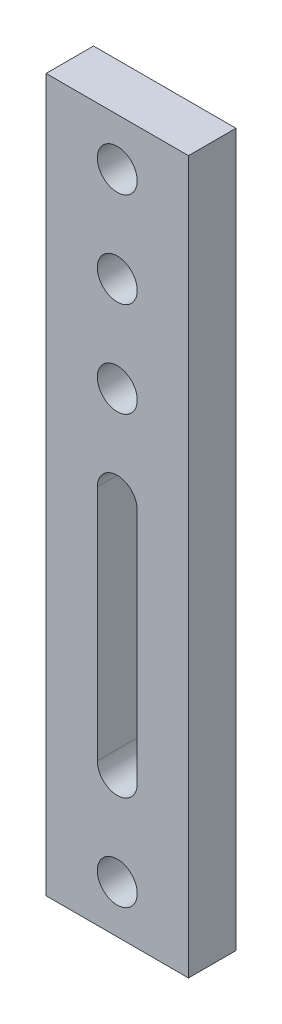
SolidWorks part; units mm, degrees
material "Простая углеродистая сталь"
ref_plane "Спереди" through (0, 0, 0) normal (0, 0, 1) x (1, 0, 0)
ref_plane "Сверху" through (0, 0, 0) normal (0, 1, 0) x (1, 0, 0)
ref_plane "Справа" through (0, 0, 0) normal (1, 0, 0) x (0, 0, -1)
sketch "Эскиз1" plane through (0, 0, 0) normal (0, 0, 1) x (1, 0, 0)
  line L1 (0, 0) -> (75, 0)
  line L2 (0, 0) -> (0, 375)
  line L3 (0, 375) -> (75, 375)
  line L4 (75, 0) -> (75, 375)
  dimension "D1" = 75
  dimension "D2" = 375
extrude "Бобышка-Вытянуть1" add sketch "Эскиз1" along normal blind 25
sketch "Эскиз2" plane through (0, 0, 25) normal (0, 0, 1) x (1, 0, 0)
  line L1 (27, 75) -> (27, 200)
  line L2 (48, 75) -> (48, 200)
  line L3 (0, 375) -> (0, 0) construction
  line L4 (0, 0) -> (75, 0) construction
  arc A0 (27, 75) -> (48, 75) centre (37.5, 75) ccw
  arc A1 (27, 200) -> (48, 200) centre (37.5, 200) cw
  circle A2 centre (37.5, 250) radius 10.5
  circle A3 centre (37.5, 300) radius 10.5
  circle A4 centre (37.5, 350) radius 10.5
  circle A5 centre (37.5, 25) radius 10.5
  point P3 (0, 0)
  point P7 (27, 137.5)
  point P10 (48, 137.5)
  point P19 (27.0379, 228.2898)
  point P20 (0, 0)
  point P21 (0, 0)
  point P22 (48.4332, 225)
  point P25 (0, 0)
  point P26 (0, 0)
  point P27 (0, 0)
  dimension "D1" = 37.5
  dimension "D2" = 75
  dimension "D3" = 3
extrude "Вырез-Вытянуть1" cut sketch "Эскиз2" against normal through all
